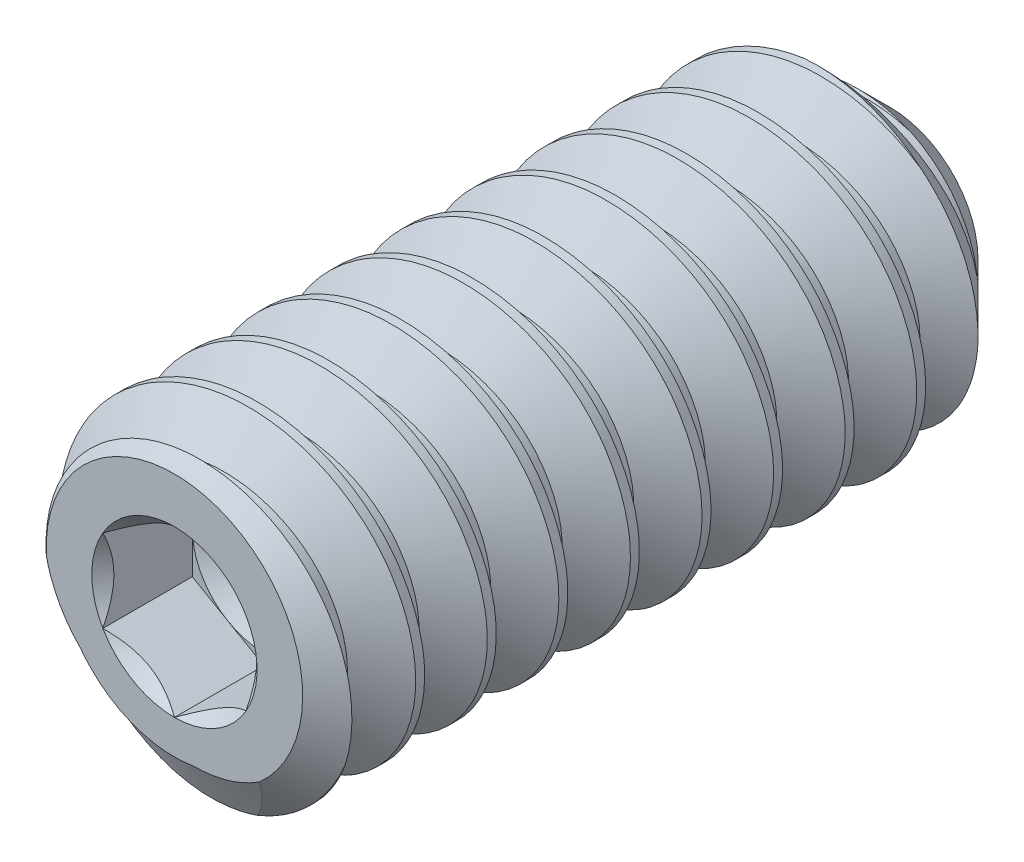
SolidWorks part; units mm, degrees
material "Cast Stainless Steel"
ref_plane "Front" through (0, 0, 0) normal (0, 0, 1) x (1, 0, 0)
ref_plane "Top" through (0, 0, 0) normal (0, 1, 0) x (1, 0, 0)
ref_plane "Right" through (0, 0, 0) normal (1, 0, 0) x (0, 0, -1)
sketch "Sketch22" plane through (0, 0, 0) normal (1, 0, 0) x (0, 0, -1)
  line L0 (-2.9408, 0) -> (-2.9408, 1.1379)
  line L1 (-2.9408, 1.1379) -> (-2.7416, 1.4224)
  line L2 (-2.7416, 1.4224) -> (2.7662, 1.4224)
  line L3 (2.7662, 1.4224) -> (3.4092, 0.7794)
  line L4 (3.4092, 0.7794) -> (2.9408, 0)
  line L5 (2.9408, 0) -> (-2.9408, 0)
  line L6 (2.9408, 0) -> (3.4092, 0) construction
  line L7 (3.4092, 0) -> (3.4092, 0.7794) construction
  line L8 (3.4092, -0.7794) -> (2.9408, 0) construction
  line L9 (-2.7416, -1.4224) -> (2.7662, -1.4224) construction
  dimension "Dia" = 2.8448
  dimension "Length" = 6.35
  dimension "D3" = 35
  dimension "D5" = 118
  dimension "D6" = 45
  dimension "D7" = 2.2758
revolve "Revolve1" add sketch "Sketch22" angle 360 about L6
ref_plane "Plane1" through (0, 0, -3.4092) normal (0, 0, 1) x (1, 0, 0)
sketch "Sketch27" plane through (0, 0, -3.4092) normal (0, 0, 1) x (1, 0, 0)
  circle A0 centre (0, 0) radius 1.4224 construction
  circle A1 centre (0, 0) radius 1.4224
curve "Helix/Spiral1" pitch 0.635 height 7.239 radius 1.4224 centre (0, 0, -3.4092) axis (0, 0, 1) start towards (0, 1, 0)
sketch "Sketch28" plane through (0, 0, 0) normal (1, 0, 0) x (0, 0, -1)
  line L0 (3.4092, 1.4224) -> (3.9648, 1.4224)
  line L1 (3.9648, 1.4224) -> (3.7425, 1.0375)
  line L2 (3.7425, 1.0375) -> (3.6314, 1.0375)
  line L3 (3.6314, 1.0375) -> (3.4092, 1.4224)
  line L4 (3.5203, 1.2299) -> (3.8537, 1.2299) construction
  line L6 (-2.7416, 1.4224) -> (2.7662, 1.4224) construction
  line L7 (3.4092, 1.6137) -> (3.4092, -1.6137) construction
  dimension "D1" = 0.1111
  dimension "D3" = 60
  dimension "D2" = 0.5556
sweep "Cut-Sweep2" cut profiles "Sketch28" path "Helix/Spiral1"
sketch "Sketch23" plane through (0, 0, 2.9408) normal (0, 0, 1) x (1, 0, 0)
  line L1 (0, 0.7332) -> (-0.635, 0.3666)
  line L2 (-0.635, 0.3666) -> (-0.635, -0.3666)
  line L3 (-0.635, -0.3666) -> (0, -0.7332)
  line L4 (0, -0.7332) -> (0.635, -0.3666)
  line L5 (0.635, -0.3666) -> (0.635, 0.3666)
  line L6 (0.635, 0.3666) -> (0, 0.7332)
  circle A0 centre (0, 0) radius 0.635 construction
  dimension "Hex" = 1.27
extrude "Cut-Extrude10" cut sketch "Sketch23" against normal blind 0.7937
sketch "Sketch24" plane through (0, 0, 2.9408) normal (0, 0, 1) x (1, 0, 0)
  circle A0 centre (0, 0) radius 0.7332
extrude "Cut-Extrude11" cut sketch "Sketch24" against normal through all draft 45
sketch "Sketch26" plane through (0, 0, 2.1471) normal (0, 0, 1) x (1, 0, 0)
  circle A0 centre (0, 0) radius 0.635 construction
  circle A1 centre (0, 0) radius 0.635
extrude "Cut-Extrude12" cut sketch "Sketch26" against normal through all draft 60
sketch "Sketch30" plane through (0, 0, 0) normal (1, 0, 0) x (0, 0, -1)
  line L0 (-2.7416, 1.4224) -> (2.7662, 1.4224) construction
  line L1 (-2.9408, 0) -> (-2.9408, 1.1379) construction
  line L2 (3.4092, 0) -> (3.4092, 0.7794) construction
  line L3 (-2.7416, -1.4224) -> (2.7662, -1.4224) construction
  point P0 (-2.9408, 1.4224)
  point P1 (3.4092, 1.4224)
  point P2 (3.4092, -1.4224)
  point P11 (1.8217, -1.4224)
  dimension "D1" = 1.5875
sketch "Sketch31" plane through (0, 0, 0) normal (1, 0, 0) x (0, 0, -1)
  line L2 (2.9408, 0) -> (3.4092, -0.7794)
  line L3 (3.4092, 0.7794) -> (2.9408, 0)
ref_axis "Axis1" through (0, 0, -3.7441) along (0, 0, 1)
equation "\"D7@Sketch22\"=\"Dia@Sketch22\"*.8"
equation "\"D1@Sketch28\" = \"D4@Helix/Spiral1\" * .175"
equation "\"D3@Helix/Spiral1\" = \"Length@Sketch22\" + \"D4@Helix/Spiral1\" + .01"
equation "\"D1@Sketch30\" = \"D4@Helix/Spiral1\" * 2.5"
equation "\"hex Depth@Cut-Extrude10\" = \"Hex@Sketch23\" * .625"
equation "\"D2@Sketch28\" = \"D4@Helix/Spiral1\" * .875"
